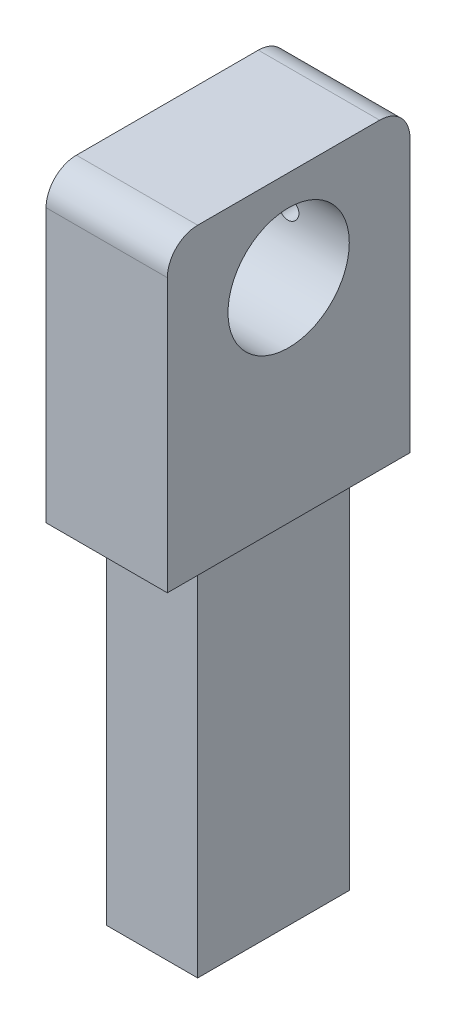
SolidWorks part; units mm, degrees
material "6061-T6 (SS)"
ref_plane "Front Plane" through (0, 0, 0) normal (0, 0, 1) x (1, 0, 0)
ref_plane "Top Plane" through (0, 0, 0) normal (0, 1, 0) x (1, 0, 0)
ref_plane "Right Plane" through (0, 0, 0) normal (1, 0, 0) x (0, 0, -1)
sketch "Sketch2" plane through (0, 0, 0) normal (0, 1, 0) x (1, 0, 0)
  line L1 (-9.525, -15.875) -> (9.525, -15.875)
  line L2 (-9.525, -15.875) -> (-9.525, 15.875)
  line L3 (-9.525, 15.875) -> (9.525, 15.875)
  line L4 (9.525, -15.875) -> (9.525, 15.875)
  line L5 (-9.525, -15.875) -> (9.525, 15.875) construction
  line L6 (-9.525, 15.875) -> (9.525, -15.875) construction
  point P0 (0, 0)
  dimension "D1" = 19.05
  dimension "D2" = 31.75
extrude "Boss-Extrude1" add sketch "Sketch2" along normal blind 76.2
sketch "Sketch3" plane through (0, 76.2, 0) normal (0, 1, 0) x (1, 0, 0)
  line L1 (-12.7, -25.4) -> (12.7, -25.4)
  line L2 (-12.7, -25.4) -> (-12.7, 25.4)
  line L3 (-12.7, 25.4) -> (12.7, 25.4)
  line L4 (12.7, -25.4) -> (12.7, 25.4)
  line L5 (-12.7, -25.4) -> (12.7, 25.4) construction
  line L6 (-12.7, 25.4) -> (12.7, -25.4) construction
  point P0 (0, 0)
  dimension "D1" = 25.4
  dimension "D2" = 50.8
extrude "Boss-Extrude2" add sketch "Sketch3" along normal blind 63.5
fillet "Fillet1" radius 6.35 2 edges at (0, 139.7, -25.4) (0, 139.7, 25.4)
sketch "Sketch4" plane through (12.7, 0, 0) normal (1, 0, 0) x (0, 0, -1)
  line L0 (-25.4, 76.2) -> (25.4, 76.2) construction
  circle A0 centre (0, 120.65) radius 12.7
  dimension "D1" = 25.4
  dimension "D2" = 44.45
extrude "Cut-Extrude1" cut sketch "Sketch4" against normal through all
sketch "Sketch5" plane through (0, 0, -25.4) normal (0, 0, -1) x (-1, 0, 0)
  circle A0 centre (0, 120.65) radius 2.1526
  dimension "D1" = 4.3053
extrude "Cut-Extrude2" cut sketch "Sketch5" against normal up to surface (12.7 mm away) up to face at (-12.7, 120.65, -12.7)
